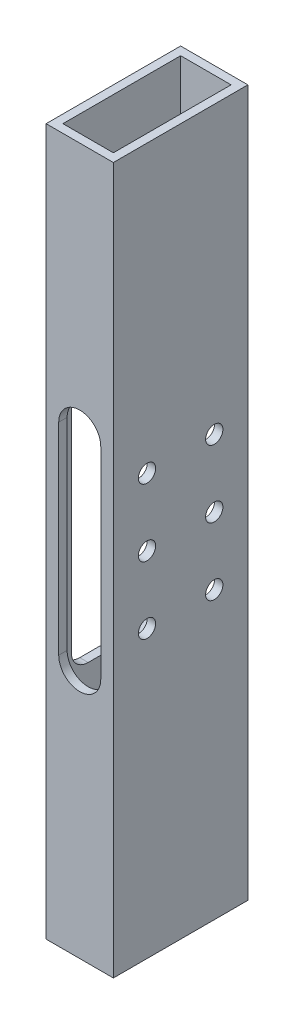
SolidWorks part; units mm, degrees
ref_plane "Front Plane" through (0, 0, 0) normal (0, 0, 1) x (1, 0, 0)
ref_plane "Top Plane" through (0, 0, 0) normal (0, 1, 0) x (1, 0, 0)
ref_plane "Right Plane" through (0, 0, 0) normal (1, 0, 0) x (0, 0, -1)
sketch "Sketch1" plane through (0, 0, 0) normal (0, 1, 0) x (1, 0, 0)
  line L0 (-9.525, 22.225) -> (9.525, 22.225)
  line L1 (-12.7, -25.4) -> (12.7, -25.4)
  line L2 (-12.7, -25.4) -> (-12.7, 25.4)
  line L3 (-12.7, 25.4) -> (12.7, 25.4)
  line L4 (12.7, -25.4) -> (12.7, 25.4)
  line L5 (-12.7, -25.4) -> (12.7, 25.4) construction
  line L6 (-12.7, 25.4) -> (12.7, -25.4) construction
  line L7 (9.525, -22.225) -> (9.525, 22.225)
  line L8 (-9.525, -22.225) -> (9.525, -22.225)
  line L9 (-9.525, -22.225) -> (-9.525, 22.225)
  point P0 (0, 0)
  dimension "D1" = 25.4
  dimension "D2" = 50.8
  dimension "D3" = 3.175
extrude "Boss-Extrude1" add sketch "Sketch1" along normal blind 266.7
sketch "Sketch2" plane through (12.7, 0, 0) normal (1, 0, 0) x (0, 0, -1)
  line L0 (-25.4, 133.35) -> (25.4, 133.35) construction
  line L1 (-25.4, 266.7) -> (-25.4, 0) construction
  line L2 (25.4, 266.7) -> (25.4, 0) construction
  line L4 (-25.4, 171.45) -> (25.4, 171.45) construction
  line L5 (-25.4, 171.45) -> (-25.4, 95.25) construction
  line L6 (-25.4, 95.25) -> (25.4, 95.25) construction
  line L7 (25.4, 171.45) -> (25.4, 95.25) construction
  line L8 (-25.4, 171.45) -> (25.4, 95.25) construction
  line L9 (-25.4, 95.25) -> (25.4, 171.45) construction
  circle A0 centre (-12.7, 158.75) radius 3.2639
  circle A1 centre (12.7, 158.75) radius 3.2639
  circle A2 centre (12.7, 133.35) radius 3.2639
  circle A3 centre (12.7, 107.95) radius 3.2639
  circle A4 centre (-12.7, 133.35) radius 3.2639
  circle A5 centre (-12.7, 107.95) radius 3.2639
  point P6 (0, 133.35)
  dimension "D4" = 6.5278
  dimension "D1" = 76.2
  dimension "D2" = 12.7
  dimension "D3" = 12.7
  dimension "D7" = 25.4
  dimension "D8" = 25.4
  dimension "D9" = 35.921
  dimension "D5" = 2
  dimension "D6" = 3
extrude "Cut-Extrude1" cut sketch "Sketch2" against normal blind 3.175
sketch "Sketch3" plane through (0, 0, 25.4) normal (0, 0, 1) x (1, 0, 0)
  line L0 (-12.7, 133.35) -> (12.7, 133.35) construction
  line L1 (-12.7, 266.7) -> (-12.7, 0) construction
  line L2 (12.7, 266.7) -> (12.7, 0) construction
  line L3 (0, 95.25) -> (0, 171.45) construction
  line L4 (-7.9375, 95.25) -> (-7.9375, 171.45)
  line L5 (7.9375, 95.25) -> (7.9375, 171.45)
  arc A0 (-7.9375, 95.25) -> (7.9375, 95.25) centre (0, 95.25) ccw
  arc A1 (7.9375, 171.45) -> (-7.9375, 171.45) centre (0, 171.45) ccw
  point P8 (0, 133.35)
  dimension "D1" = 76.2
  dimension "D2" = 15.875
extrude "Cut-Extrude2" cut sketch "Sketch3" against normal through all
sketch "Sketch4" plane through (-12.7, 0, 0) normal (-1, 0, 0) x (0, 0, 1)
  line L0 (25.4, 266.7) -> (25.4, 0) construction
  line L1 (19.05, 180.975) -> (-19.05, 180.975)
  line L2 (19.05, 180.975) -> (19.05, 85.725)
  line L3 (19.05, 85.725) -> (-19.05, 85.725)
  line L4 (-19.05, 180.975) -> (-19.05, 85.725)
  line L5 (-25.4, 133.35) -> (25.4, 133.35) construction
  line L6 (-25.4, 266.7) -> (-25.4, 0) construction
  point P10 (-19.05, 133.35)
  dimension "D1" = 38.1
  dimension "D2" = 6.35
  dimension "D3" = 95.25
extrude "Cut-Extrude3" cut sketch "Sketch4" against normal blind 6.35
fillet "Fillet1" radius 6.35 4 edges at (-11.1125, 85.725, -19.05) (-11.1125, 85.725, 19.05) (-11.1125, 180.975, 19.05) (-11.1125, 180.975, -19.05)
